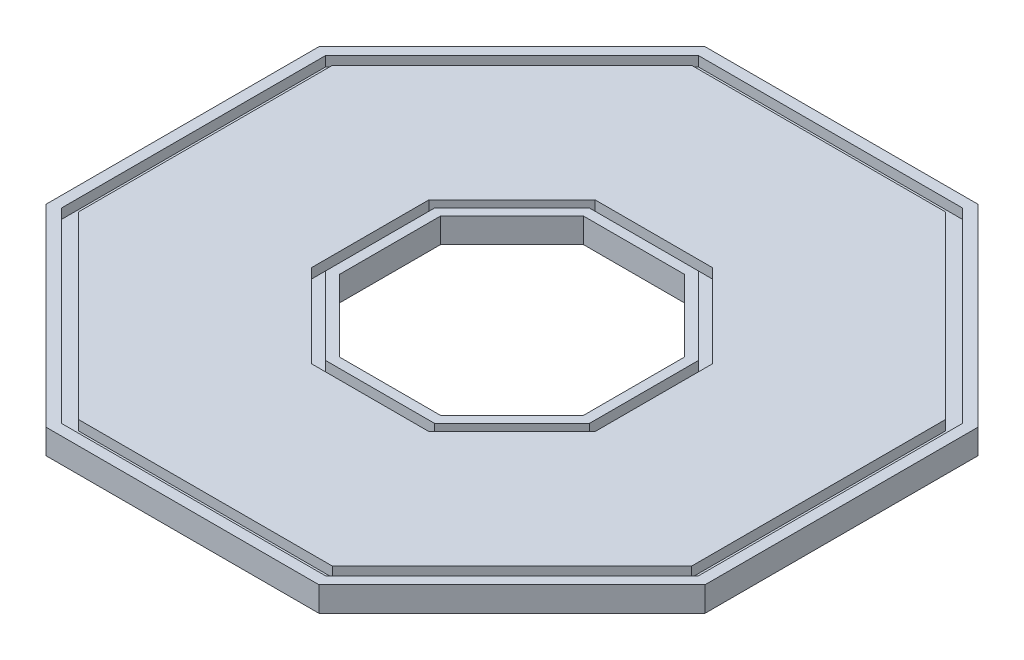
SolidWorks part; units mm, degrees
ref_plane "정면" through (0, 0, 0) normal (0, 0, 1) x (1, 0, 0)
ref_plane "윗면" through (0, 0, 0) normal (0, 1, 0) x (1, 0, 0)
ref_plane "우측면" through (0, 0, 0) normal (1, 0, 0) x (0, 0, -1)
sketch "스케치1" plane through (0, 0, 0) normal (0, 1, 0) x (1, 0, 0)
  line L0 (-55, 0) -> (55, 0) construction
  line L1 (13.2795, -32.0597) -> (32.0597, -13.2795)
  line L2 (32.0597, -13.2795) -> (32.0597, 13.2795)
  line L3 (32.0597, 13.2795) -> (13.2795, 32.0597)
  line L4 (13.2795, 32.0597) -> (-13.2795, 32.0597)
  line L5 (-13.2795, 32.0597) -> (-32.0597, 13.2795)
  line L6 (-32.0597, 13.2795) -> (-32.0597, -13.2795)
  line L7 (-32.0597, -13.2795) -> (-13.2795, -32.0597)
  line L8 (-13.2795, -32.0597) -> (13.2795, -32.0597)
  line L9 (13.7766, -33.2597) -> (33.2597, -13.7766)
  line L10 (33.2597, -13.7766) -> (33.2597, 13.7766)
  line L11 (33.2597, 13.7766) -> (13.7766, 33.2597)
  line L12 (13.7766, 33.2597) -> (-13.7766, 33.2597)
  line L13 (-13.7766, 33.2597) -> (-33.2597, 13.7766)
  line L14 (-33.2597, 13.7766) -> (-33.2597, -13.7766)
  line L15 (-33.2597, -13.7766) -> (-13.7766, -33.2597)
  line L16 (-13.7766, -33.2597) -> (13.7766, -33.2597)
  line L17 (12.7825, -30.8597) -> (30.8597, -12.7825)
  line L18 (30.8597, -12.7825) -> (30.8597, 12.7825)
  line L19 (30.8597, 12.7825) -> (12.7825, 30.8597)
  line L20 (12.7825, 30.8597) -> (-12.7825, 30.8597)
  line L21 (-12.7825, 30.8597) -> (-30.8597, 12.7825)
  line L22 (-30.8597, 12.7825) -> (-30.8597, -12.7825)
  line L23 (-30.8597, -12.7825) -> (-12.7825, -30.8597)
  line L24 (-12.7825, -30.8597) -> (12.7825, -30.8597)
  circle A0 centre (0, 0) radius 34.7011 construction
  dimension "D1" = 72
  dimension "D2" = 1.2
  dimension "D3" = 1.2
extrude "보스-돌출1" add sketch "스케치1" along normal blind 2.5 contours L23 L24 L17 L18 L19 L20 L21 L22 | L7 L8 L1 L2 L3 L4 L5 L6 L24 L23 L22 L21 L20 L19 L18 L17 | L15 L16 L9 L10 L11 L12 L13 L14 L8 L7 L6 L5 L4 L3 L2 L1 region at (0, 0, 31.1529) region at (0, 0, 32.3189) region at (0, 0, 0)
sketch "스케치2" plane through (0, 2.5, 0) normal (0, 1, 0) x (1, 0, 0)
  line L0 (33.2597, -13.7766) -> (33.2597, 13.7766) construction
  line L1 (13.3174, -32.151) -> (32.151, -13.3174)
  line L2 (32.151, -13.3174) -> (32.151, 13.3174)
  line L3 (32.151, 13.3174) -> (13.3174, 32.151)
  line L4 (13.3174, 32.151) -> (-13.3174, 32.151)
  line L5 (-13.3174, 32.151) -> (-32.151, 13.3174)
  line L6 (-32.151, 13.3174) -> (-32.151, -13.3174)
  line L7 (-32.151, -13.3174) -> (-13.3174, -32.151)
  line L8 (-13.3174, -32.151) -> (13.3174, -32.151)
  line L9 (12.8203, -30.951) -> (30.951, -12.8203)
  line L10 (30.951, -12.8203) -> (30.951, 12.8203)
  line L11 (30.951, 12.8203) -> (12.8203, 30.951)
  line L12 (12.8203, 30.951) -> (-12.8203, 30.951)
  line L13 (-12.8203, 30.951) -> (-30.951, 12.8203)
  line L14 (-30.951, 12.8203) -> (-30.951, -12.8203)
  line L15 (-30.951, -12.8203) -> (-12.8203, -30.951)
  line L16 (-12.8203, -30.951) -> (12.8203, -30.951)
  circle A0 centre (0, 0) radius 34.8 construction
  dimension "D1" = 69.6
  dimension "D2" = 1.2
extrude "컷-돌출1" cut sketch "스케치2" against normal blind 1
sketch "스케치4" plane through (0, 2.5, 0) normal (0, 1, 0) x (1, 0, 0)
  line L0 (30.951, -12.8203) -> (30.951, 12.8203) construction
  line L1 (5.9316, -14.3201) -> (14.3201, -5.9316)
  line L2 (14.3201, -5.9316) -> (14.3201, 5.9316)
  line L3 (14.3201, 5.9316) -> (5.9316, 14.3201)
  line L4 (5.9316, 14.3201) -> (-5.9316, 14.3201)
  line L5 (-5.9316, 14.3201) -> (-14.3201, 5.9316)
  line L6 (-14.3201, 5.9316) -> (-14.3201, -5.9316)
  line L7 (-14.3201, -5.9316) -> (-5.9316, -14.3201)
  line L8 (-5.9316, -14.3201) -> (5.9316, -14.3201)
  line L9 (5.5174, -13.3201) -> (13.3201, -5.5174)
  line L10 (13.3201, -5.5174) -> (13.3201, 5.5174)
  line L11 (13.3201, 5.5174) -> (5.5174, 13.3201)
  line L12 (5.5174, 13.3201) -> (-5.5174, 13.3201)
  line L13 (-5.5174, 13.3201) -> (-13.3201, 5.5174)
  line L14 (-13.3201, 5.5174) -> (-13.3201, -5.5174)
  line L15 (-13.3201, -5.5174) -> (-5.5174, -13.3201)
  line L16 (-5.5174, -13.3201) -> (5.5174, -13.3201)
  line L17 (5.1032, -12.3201) -> (12.3201, -5.1032)
  line L18 (12.3201, -5.1032) -> (12.3201, 5.1032)
  line L19 (12.3201, 5.1032) -> (5.1032, 12.3201)
  line L20 (5.1032, 12.3201) -> (-5.1032, 12.3201)
  line L21 (-5.1032, 12.3201) -> (-12.3201, 5.1032)
  line L22 (-12.3201, 5.1032) -> (-12.3201, -5.1032)
  line L23 (-12.3201, -5.1032) -> (-5.1032, -12.3201)
  line L24 (-5.1032, -12.3201) -> (5.1032, -12.3201)
  circle A0 centre (0, 0) radius 15.5 construction
  dimension "31" = 31
  dimension "D2" = 1
  dimension "D3" = 1
extrude "컷-돌출2" cut sketch "스케치4" against normal blind 3.8 contours L23 L24 L17 L18 L19 L20 L21 L22 region at (0, 2.5, 0)
extrude "컷-돌출3" cut sketch "스케치4<3>" against normal blind 1 contours L7 L8 L1 L2 L3 L4 L5 L6 L16 L15 L14 L13 L12 L11 L10 L9 region at (0, 2.5, 13.9151)
sketch "스케치4<3>" plane through (0, 2.5, 0) normal (0, 1, 0) x (1, 0, 0) same geometry as "스케치4"
